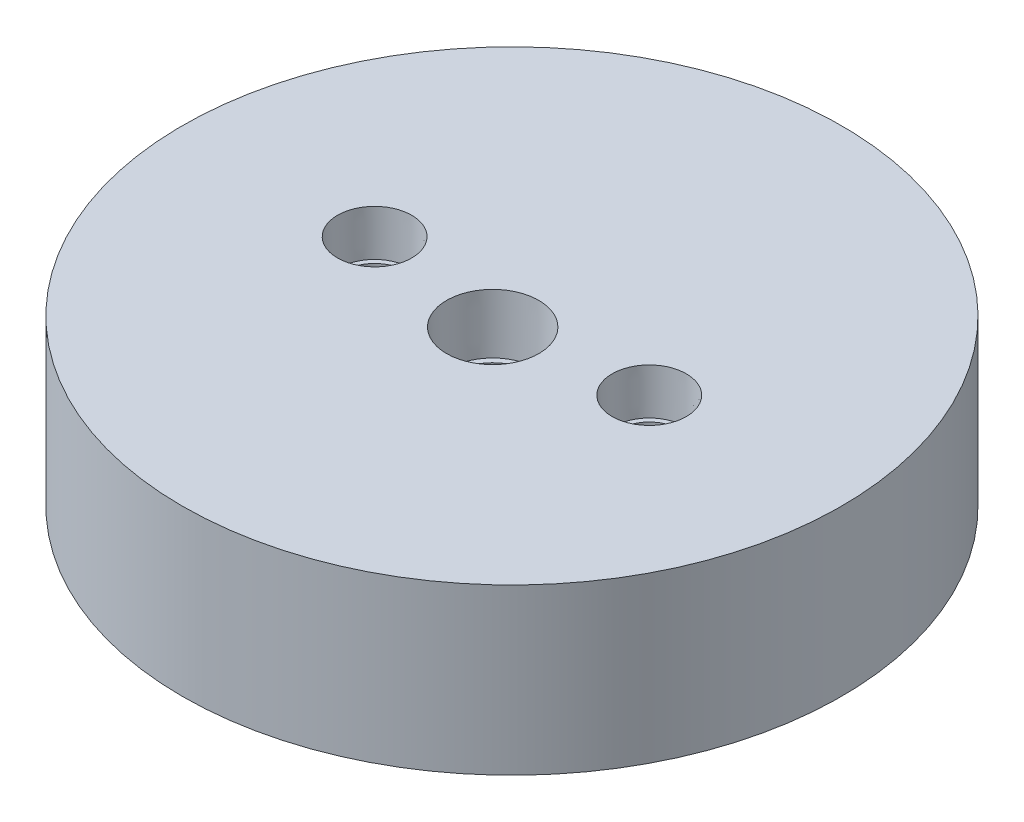
SolidWorks part; units mm, degrees
ref_plane "Front Plane" through (0, 0, 0) normal (0, 0, 1) x (1, 0, 0)
ref_plane "Top Plane" through (0, 0, 0) normal (0, 1, 0) x (1, 0, 0)
ref_plane "Right Plane" through (0, 0, 0) normal (1, 0, 0) x (0, 0, -1)
ref_axis "Axial" through (0, 53.34, 0) along (0, -1, 0)
ref_plane "Bottom Plane" through (0, -50.8, 0) normal (0, 1, 0) x (1, 0, 0)
sketch "Sketch1" plane through (0, 0, 0) normal (0, 1, 0) x (1, 0, 0)
  circle A0 centre (0, 0) radius 76.2
  dimension "D1" = 152.4
extrude "Billet" add sketch "Sketch1" against normal blind 50.8
sketch "Sketch3" plane through (0, -50.8, 0) normal (0, 1, 0) x (1, 0, 0)
  line L0 (0, 81.5114) -> (0, -83.2162) construction
  circle A0 centre (0, 0) radius 19.05
  dimension "D1" = 38.1
  dimension "D2" = 0
extrude "Lox Plate" cut sketch "Sketch3" along normal blind 13.97
sketch "Sketch5" plane through (0, -50.8, 0) normal (0, 1, 0) x (1, 0, 0)
  line L0 (0, 57.2178) -> (0, -49.9723) construction
  circle A0 centre (0, 0) radius 13.97
  dimension "D1" = 27.94
  dimension "D2" = 0
extrude "Lox Dome" cut sketch "Sketch5" along normal blind 20.32
sketch "Sketch7" plane through (0, 0, 0) normal (0, 1, 0) x (1, 0, 0)
  circle A1 centre (0, 0) radius 76.2
  dimension "D2" = 152.4
extrude "Top Mill" cut sketch "Sketch7" against normal blind 12.7
sketch "Sketch12" plane through (0, -50.8, 0) normal (0, 1, 0) x (1, 0, 0)
  circle A0 centre (0, 0) radius 60.96
  dimension "D1" = 121.92
extrude "Kerosene Plate" cut sketch "Sketch12" along normal blind 10.16
hole_wizard "Lox Inlet-1/2 NPT Tapped Hole3" positions "Sketch20" profile "Sketch21" size "1/2" standard "ANSI Inch" end condition through all
sketch "Sketch20" plane through (0, -12.7, 0) normal (0, 1, 0) x (1, 0, 0)
  line L0 (0, 40.1697) -> (0, -38.6779) construction
  point P8 (0, -4.445)
  dimension "D1" = 4.445
sketch "Sketch21" plane through (0, -12.7, 4.445) normal (1, 0, 0) x (0, 0, 1)
  line L0 (0, 0) -> (0, 38.1)
  line L1 (0, 38.1) -> (8.9281, 38.1)
  line L2 (-10.2617, 13.462) -> (-10.6647, 0) construction
  line L3 (8.9281, 38.1) -> (8.9281, 13.462)
  line L4 (8.9281, 13.462) -> (10.2617, 13.462)
  line L5 (10.2617, 13.462) -> (10.6647, 0)
  line L7 (10.6647, 0) -> (0, 0)
  line L8 (0, -6.35) -> (0, 107.95) construction
  line L11 (-8.9281, 13.462) -> (-10.2617, 13.462) construction
  dimension "Thru Tap Drill Dia." = 17.8562
  dimension "Thru Tap Drill Depth" = 38.1
  dimension "Thread Dia." = 21.3295
  dimension "Thread Angle" = 3.43
  dimension "Thread Depth" = 13.462
hole_wizard "Kerosene Inlet-3/8 NPT Tapped Hole1" positions "Sketch24" profile "Sketch25" size "3/8" standard "ANSI Inch" end condition through all
sketch "Sketch24" plane through (0, -12.7, 0) normal (0, 1, 0) x (1, 0, 0)
  point P0 (-31.75, 0)
  point P2 (31.75, 0)
  dimension "D1" = 31.75
  dimension "D2" = 31.75
sketch "Sketch25" plane through (-31.75, -12.7, 0) normal (1, 0, 0) x (0, 0, 1)
  line L0 (0, 0) -> (0, 38.1)
  line L1 (0, 38.1) -> (7.1374, 38.1)
  line L2 (-8.2632, 10.414) -> (-8.575, 0) construction
  line L3 (7.1374, 38.1) -> (7.1374, 10.414)
  line L4 (7.1374, 10.414) -> (8.2632, 10.414)
  line L5 (8.2632, 10.414) -> (8.575, 0)
  line L7 (8.575, 0) -> (0, 0)
  line L8 (0, -6.35) -> (0, 107.95) construction
  line L11 (-7.1374, 10.414) -> (-8.2632, 10.414) construction
  dimension "Thru Tap Drill Dia." = 14.2748
  dimension "Thru Tap Drill Depth" = 38.1
  dimension "Thread Dia." = 17.15
  dimension "Thread Angle" = 3.43
  dimension "Thread Depth" = 10.414
